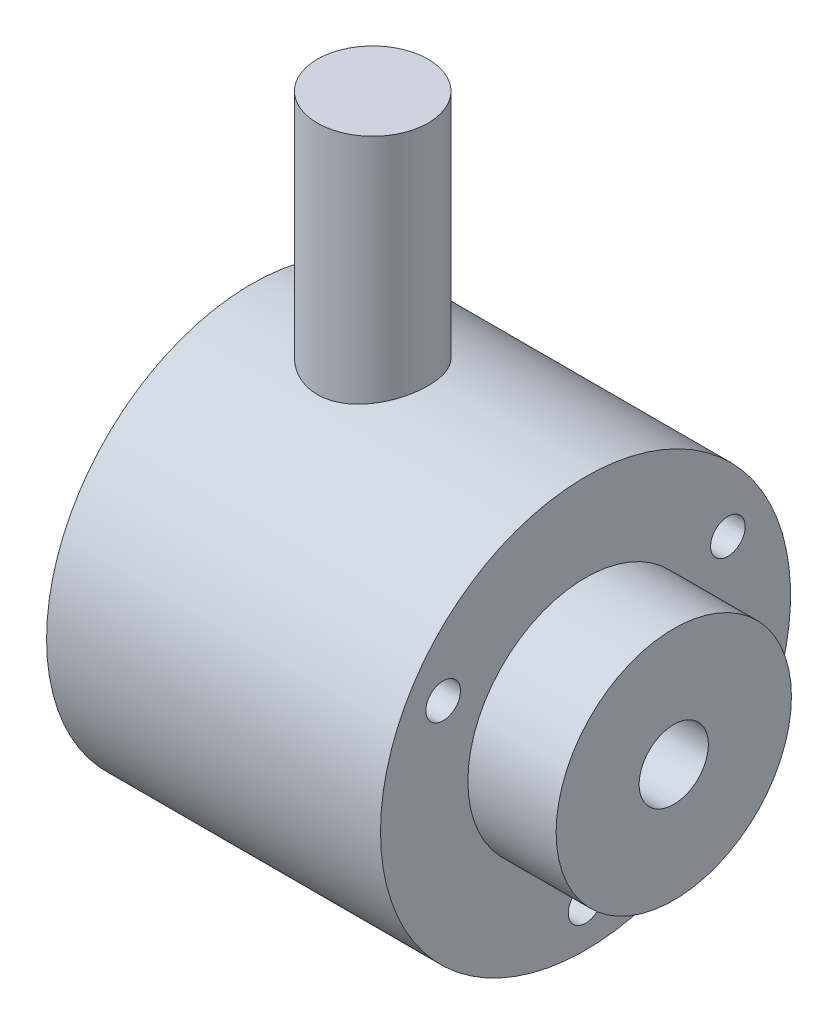
SolidWorks part; units mm, degrees
ref_plane "Plan de face" through (0, 0, 0) normal (0, 0, 1) x (1, 0, 0)
ref_plane "Plan de dessus" through (0, 0, 0) normal (0, 1, 0) x (1, 0, 0)
ref_plane "Plan de droite" through (0, 0, 0) normal (1, 0, 0) x (0, 0, -1)
sketch "Esquisse1" plane through (0, 0, 0) normal (0, 0, 1) x (1, 0, 0)
  line L0 (0, 0) -> (24.4, 0)
  line L1 (24.4, 0) -> (24.4, 6.8)
  line L2 (24.4, 6.8) -> (19.3, 6.8)
  line L3 (19.3, 6.8) -> (19.3, 11.85)
  line L4 (19.3, 11.85) -> (0, 11.85)
  line L5 (0, 11.85) -> (0, 0)
  dimension "D1" = 11.85
  dimension "D2" = 19.3
  dimension "D3" = 6.8
  dimension "D4" = 5.1
revolve "Révolution2" add sketch "Esquisse1" angle 360 about L0
sketch "Esquisse2" plane through (0, 0, 0) normal (0, 1, 0) x (1, 0, 0)
  line L0 (0, 11.85) -> (0, -11.85) construction
  circle A0 centre (7, 0) radius 3.2
  dimension "D1" = 6.4
  dimension "D2" = 7
extrude "Boss.-Extru.1" add sketch "Esquisse2" along normal blind 25
sketch "Esquisse3" plane through (24.4, 0, 0) normal (1, 0, 0) x (0, 0, -1)
  circle A0 centre (0, 0) radius 2
  dimension "D1" = 4
extrude "Enlèv. mat.-Extru.1" cut sketch "Esquisse3" against normal blind 14
ref_axis "Axe2" through (60.1402, 0, 0) along (-1, 0, 0)
sketch "Esquisse4" plane through (19.3, 0, 0) normal (1, 0, 0) x (0, 0, -1)
  line L0 (0, 13.42) -> (0, -13.42) construction
  circle A0 centre (0, -9.5) radius 1
  circle A1 centre (0, 0) radius 11.85 construction
  circle A2 centre (-8.2272, 4.75) radius 1
  circle A3 centre (8.2272, 4.75) radius 1
  point P2 (0, -11.85)
  dimension "D1" = 2
  dimension "D2" = 60
  dimension "D3" = 60
  dimension "D4" = 9.5
  dimension "D5" = 9.5
extrude "Enlèv. mat.-Extru.2" cut sketch "Esquisse4" against normal blind 4
